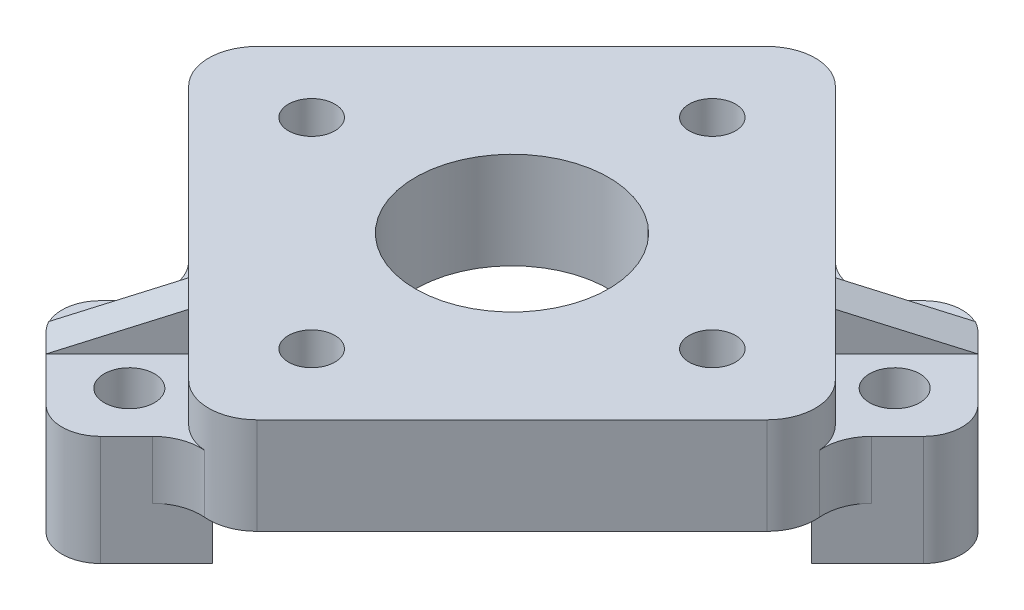
SolidWorks part; units mm, degrees
ref_plane "Front Plane" through (0, 0, 0) normal (0, 0, 1) x (1, 0, 0)
ref_plane "Top Plane" through (0, 0, 0) normal (0, 1, 0) x (1, 0, 0)
ref_plane "Right Plane" through (0, 0, 0) normal (1, 0, 0) x (0, 0, -1)
sketch "Sketch1" plane through (0, 0, 0) normal (0, 1, 0) x (1, 0, 0)
  line L0 (0, 10.365) -> (0, -10.365) construction
  line L1 (10.365, 0) -> (-10.365, 0) construction
  line L2 (0, 10.365) -> (10.365, 0) construction
  line L3 (10.365, 0) -> (0, -10.365) construction
  line L4 (0, -10.365) -> (-10.365, 0) construction
  line L8 (-10.365, 0) -> (0, 10.365) construction
  line L9 (1.7678, 14.9612) -> (14.9612, 1.7678)
  line L10 (14.9612, -1.7678) -> (1.7678, -14.9612)
  line L11 (-1.7678, -14.9612) -> (-14.9612, -1.7678)
  line L12 (-14.9612, 1.7678) -> (-1.7678, 14.9612)
  line L13 (16.729, 0) -> (0, -16.729) construction
  line L14 (0, -16.729) -> (-16.729, 0) construction
  line L15 (0, 16.729) -> (16.729, 0) construction
  line L16 (-16.729, 0) -> (0, 16.729) construction
  circle A7 centre (0, 10.365) radius 0.5
  circle A8 centre (0, -10.365) radius 0.5
  circle A9 centre (10.365, 0) radius 0.5
  circle A10 centre (-10.365, 0) radius 0.5
  circle A11 centre (0, 0) radius 5
  arc A12 (1.7678, -14.9612) -> (-1.7678, -14.9612) centre (0, -13.1934) cw
  arc A13 (14.9612, 1.7678) -> (14.9612, -1.7678) centre (13.1934, 0) cw
  arc A14 (-14.9612, -1.7678) -> (-14.9612, 1.7678) centre (-13.1934, 0) cw
  arc A15 (1.7678, 14.9612) -> (-1.7678, 14.9612) centre (0, 13.1934) ccw
  dimension "D2" = 1
  dimension "D3" = 10
  dimension "D4" = 4.5
  dimension "D5" = 2.5
  dimension "D1" = 20.73
extrude "Boss-Extrude1" add sketch "Sketch1" along normal blind 5
sketch "Sketch4" plane through (0, 0, 0) normal (0, -1, 0) x (1, 0, 0)
  circle A0 centre (0, 10.365) radius 3
  circle A1 centre (10.365, 0) radius 3
  circle A2 centre (-10.365, 0) radius 3
  circle A3 centre (0, -10.365) radius 3
  point P0 (0, 10.365)
  point P3 (10.365, 0)
  point P6 (-10.365, 0)
  point P9 (0, -10.365)
  dimension "D1" = 6
ref_plane "Plane1" through (0, -2.7, 0) normal (0, 1, 0) x (1, 0, 0)
ref_plane "Plane2" through (8.3645, 0, 8.3645) normal (0.7071, 0, 0.7071) x (0.7071, 0, -0.7071)
ref_plane "Plane3" through (2.7076, 0, 2.7076) normal (0.7071, 0, 0.7071) x (0.7071, 0, -0.7071)
sketch "Sketch3" plane through (0, -2.7, 0) normal (0, 1, 0) x (1, 0, 0)
  line L0 (-8.3645, 8.3645) -> (8.3645, -8.3645) construction
  line L1 (-1.7678, 14.9612) -> (-14.9612, 1.7678) construction
  line L2 (1.7678, -14.9612) -> (14.9612, -1.7678) construction
  line L3 (9.8995, 9.8995) -> (14.8492, 4.9497) construction
  line L5 (10.5375, 4.9497) -> (14.8492, 0.638)
  line L12 (14.9612, 1.7678) -> (1.7678, 14.9612) construction
  line L13 (14.8492, 0.638) -> (19.161, 4.9497)
  line L20 (0, 0) -> (9.8995, 9.8995) construction
  line L21 (14.9612, 1.7678) -> (1.7678, 14.9612) construction
  line L22 (19.161, 4.9497) -> (14.8492, 9.2615)
  line L23 (14.8492, 9.2615) -> (10.5375, 4.9497)
  line L24 (19.161, 4.9497) -> (10.5375, 4.9497) construction
  line L25 (-4.9497, -19.161) -> (-4.9497, -10.5375) construction
  line L26 (-9.8995, -9.8995) -> (-4.9497, -14.8492) construction
  line L27 (-9.2615, -14.8492) -> (-4.9497, -10.5375)
  line L28 (-4.9497, -19.161) -> (-9.2615, -14.8492)
  line L29 (-0.638, -14.8492) -> (-4.9497, -19.161)
  line L30 (-4.9497, -10.5375) -> (-0.638, -14.8492)
  line L31 (10.5375, 4.9497) -> (8.7697, 6.7175)
  line L32 (8.7697, 6.7175) -> (13.0815, 11.0293)
  line L33 (13.0815, 11.0293) -> (14.8492, 9.2615)
  line L34 (-4.9497, -10.5375) -> (-6.7175, -8.7697)
  line L35 (-6.7175, -8.7697) -> (-11.0293, -13.0815)
  line L36 (-11.0293, -13.0815) -> (-9.2615, -14.8492)
  circle A2 centre (14.8492, 4.9497) radius 1.3
  circle A3 centre (-4.9497, -14.8492) radius 1.3
  dimension "D1" = 2.6
  dimension "D2" = 7
  dimension "D3" = 3.0489
  dimension "D4" = 14
  dimension "D5" = 2.5
extrude "Boss-Extrude4" add sketch "Sketch3" along normal offset from surface (5.7 mm away) 3 contours L30 L27 L28 L29 A3 | L35 L36 L27 L34 | L22 L23 L5 L13 A2 | L33 L32 L31 L23 region at (12.7796, -2.7, -7.0194) region at (11.8095, -2.7, -7.9895) region at (-7.9895, -2.7, 11.8095) region at (-7.0194, -2.7, 12.7796) up to face at (-10.365, 0, 0.5)
sketch "Sketch7" plane through (2.7076, 0, 2.7076) normal (0.7071, 0, 0.7071) x (0.7071, 0, -0.7071)
  line L0 (11.8292, 5) -> (17.0489, 3)
  line L1 (-11.8292, 5) -> (-17.0489, 3)
  line L2 (-17.0489, 3) -> (-11.8292, 3)
  line L3 (-11.8292, 3) -> (-11.8292, 5)
  line L4 (11.8292, 5) -> (11.8292, 3)
  line L5 (11.8292, 3) -> (17.0489, 3)
extrude "Boss-Extrude6" add sketch "Sketch7" along normal mid plane 2
fillet "Fillet1" radius 2.5 4 edges at (-7.3384, 1.5, 9.3906) (9.3906, 1.5, -7.3384) (15.3953, 1.5, -1.184) (-1.184, 1.5, 15.3953)
fillet "Fillet2" radius 2 4 edges at (-11.0293, 0.15, 13.0815) (-4.9497, 0.15, 19.161) (13.0815, 0.15, -11.0293) (19.161, 0.15, -4.9497)
hole_wizard "CSK for M2 Flat Head Machine Screw5" positions "Sketch4" profile "Sketch11" countersink size "M2" standard "ANSI Metric"
sketch "Sketch11" plane through (0, 0, 10.365) normal (1, 0, 0) x (0, 0, -1)
  line L0 (0, 0) -> (0, 43.651)
  line L1 (0, 43.651) -> (1.2, 42.93)
  line L2 (1.2, 42.93) -> (1.2, 1)
  line L3 (1.2, 1) -> (2.2, 0)
  line L5 (2.2, 0) -> (0, 0)
  line L6 (-1.2, 1) -> (-2.2, 0) construction
  line L10 (0, 43.651) -> (-1.2, 42.93) construction
  line L11 (0, -6.35) -> (0, 107.95) construction
  dimension "Hole Dia." = 2.4
  dimension "Hole Depth" = 42.93
  dimension "Near C'Sink Dia." = 4.4
  dimension "Near C'Sink Angle" = 90
  dimension "Drill Angle" = 118
